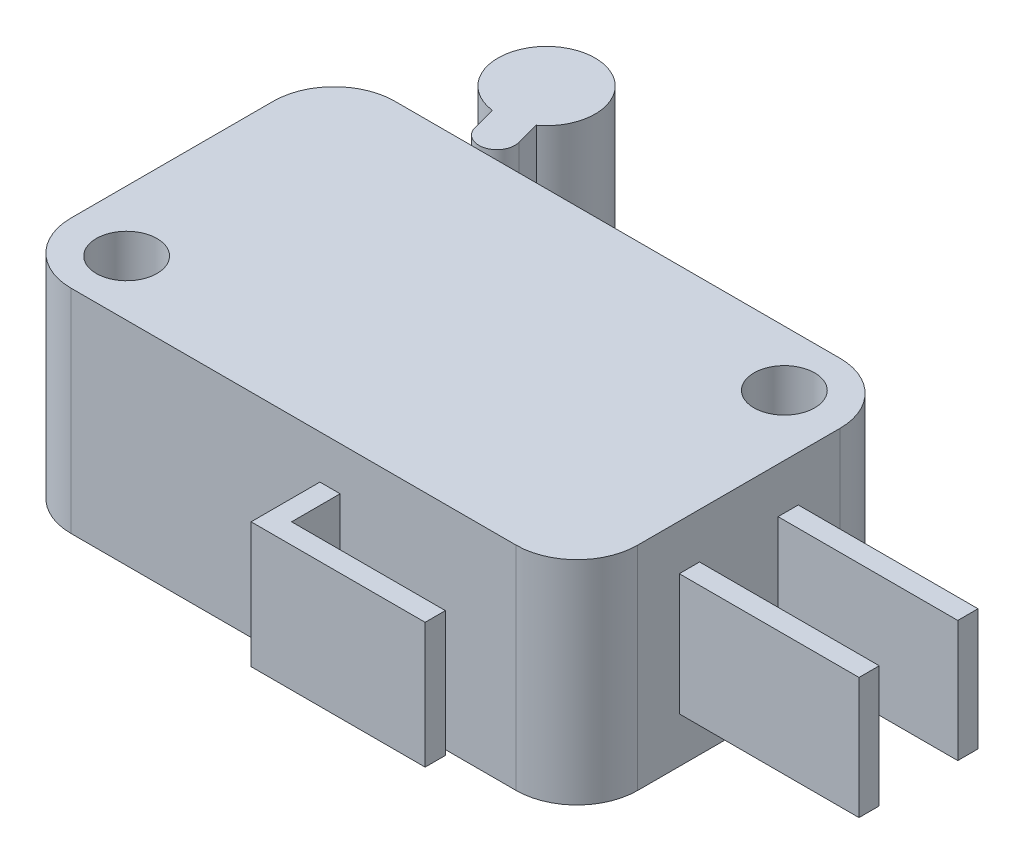
SolidWorks part; units mm, degrees
other "标注1"
sketch "草图9" plane through (22.88, 5.25, -16.5) normal (0.284, 0.954, -0.0961) x (0.0916, -0.1268, -0.9877)
material "304不锈钢"
ref_plane "前视基准面" through (0, 0, 0) normal (0, 0, 1) x (1, 0, 0)
ref_plane "上视基准面" through (0, 0, 0) normal (0, 1, 0) x (1, 0, 0)
ref_plane "右视基准面" through (0, 0, 0) normal (1, 0, 0) x (0, 0, -1)
sketch "草图1" plane through (0, 0, 0) normal (0, 1, 0) x (1, 0, 0)
  line L1 (-14, 8) -> (14, 8)
  line L2 (-14, 8) -> (-14, -8)
  line L3 (-14, -8) -> (14, -8)
  line L4 (14, 8) -> (14, -8)
  line L5 (-14, 8) -> (14, -8) construction
  line L6 (-14, -8) -> (14, 8) construction
  point P0 (0, 0)
  dimension "D1" = 16
  dimension "D2" = 28
extrude "凸台-拉伸1" add sketch "草图1" along normal mid plane 10.5
fillet "圆角1" radius 3 4 edges at (14, 0, 8) (-14, 0, -8) (14, 0, -8) (-14, 0, 8)
sketch "草图2" plane through (0, 5.25, 0) normal (0, 1, 0) x (1, 0, 0)
  line L1 (-11, -5.25) -> (11, -5.25) construction
  line L2 (-11, -5.25) -> (-11, 5.25) construction
  line L3 (-11, 5.25) -> (11, 5.25) construction
  line L4 (11, -5.25) -> (11, 5.25) construction
  line L5 (0, 5.25) -> (0, -5.25) construction
  line L6 (-11, 0) -> (11, 0) construction
  circle A0 centre (11, 5.25) radius 1.5
  circle A1 centre (-11, -5.25) radius 1.5
  point P2 (0, 0)
  dimension "D1" = 3
  dimension "D2" = 3
  dimension "D3" = 10.5
  dimension "D4" = 22
extrude "切除-拉伸1" cut sketch "草图2" against normal up to next
sketch "草图3" plane through (0, 0, 8) normal (0, 0, 1) x (1, 0, 0)
  line L0 (-14, -5.25) -> (-14, 5.25) construction
  line L1 (1.3, 3.1) -> (9.9, 3.1)
  line L2 (1.3, 3.1) -> (1.3, -3.1)
  line L3 (1.3, -3.1) -> (9.9, -3.1)
  line L4 (9.9, 3.1) -> (9.9, -3.1)
  line L5 (1.3, 3.1) -> (9.9, -3.1) construction
  line L6 (1.3, -3.1) -> (9.9, 3.1) construction
  point P0 (5.6, 0)
  dimension "D1" = 6.2
  dimension "D2" = 8.6
  dimension "D3" = 15.3
extrude "凸台-拉伸2" add sketch "草图3" along normal blind 3.4
sketch "草图4" plane through (0, 3.1, 0) normal (0, 1, 0) x (1, 0, 0)
  line L0 (9.9, -11.4) -> (1.3, -11.4) construction
  line L1 (9.9, -8) -> (2.3, -8)
  line L2 (9.9, -8) -> (9.9, -10.4)
  line L3 (9.9, -10.4) -> (2.3, -10.4)
  line L4 (2.3, -8) -> (2.3, -10.4)
  line L5 (1.3, -11.4) -> (1.3, -8) construction
  dimension "D1" = 1
  dimension "D2" = 1
extrude "切除-拉伸2" cut sketch "草图4" against normal up to next
sketch "草图5" plane through (0, 0, 0) normal (0, 1, 0) x (1, 0, 0)
  line L0 (14, -5) -> (14, 5) construction
  line L1 (14, 2.94) -> (22.88, 2.94)
  line L2 (14, 2.94) -> (14, 1.94)
  line L3 (14, 1.94) -> (22.88, 1.94)
  line L4 (22.88, 2.94) -> (22.88, 1.94)
  line L5 (-14, 5) -> (-14, -5) construction
  line L6 (14, -1.94) -> (22.88, -1.94)
  line L7 (14, -1.94) -> (14, -2.94)
  line L8 (14, -2.94) -> (22.88, -2.94)
  line L9 (22.88, -1.94) -> (22.88, -2.94)
  line L10 (14, 1.94) -> (14, -1.94) construction
  point P12 (14, 0)
  dimension "D1" = 1
  dimension "D2" = 1
  dimension "D3" = 5.88
  dimension "D4" = 36.88
extrude "凸台-拉伸3" add sketch "草图5" along normal mid plane 6
sketch "草图6" plane through (0, 0, -8) normal (0, 0, -1) x (-1, 0, 0)
  line L0 (14, 5.25) -> (14, -5.25) construction
  line L1 (11.3, 2.1) -> (8.5, 2.1)
  line L2 (11.3, 2.1) -> (11.3, -2.1)
  line L3 (11.3, -2.1) -> (8.5, -2.1)
  line L4 (8.5, 2.1) -> (8.5, -2.1)
  line L5 (11.3, 2.1) -> (8.5, -2.1) construction
  line L6 (11.3, -2.1) -> (8.5, 2.1) construction
  point P0 (9.9, 0)
  dimension "D1" = 2.8
  dimension "D2" = 5.5
  dimension "D3" = 4.2
extrude "凸台-拉伸4" add sketch "草图6" along normal blind 3
fillet "圆角2" radius 1.2 2 edges at (-11.3, 0, -11) (-8.5, 0, -11)
sketch "草图7" plane through (0, 0, 0) normal (0, 1, 0) x (1, 0, 0)
  line L0 (2.6, 8) -> (2.6, 9.1858)
  line L1 (11, 8) -> (-11, 8) construction
  line L2 (2.6, 9.1858) -> (-9.5237, 10.987)
  line L3 (14, -5) -> (14, 5) construction
  line L4 (-11, -8) -> (11, -8) construction
  arc A0 (-8.5, 9.8) -> (-9.7, 11) centre (-9.7, 9.8) ccw construction
  circle A1 centre (-9.6, 14.1) radius 2.4
  dimension "D2" = 24.5
  dimension "D3" = 4.8
  dimension "D1" = 11.4
extrude "拉伸-薄壁2" add sketch "草图7" along normal mid plane 3 thin contours L0 L2 thin type mid plane wall 1
extrude "凸台-拉伸5" add sketch "草图7<3>" along normal mid plane 7.1 separate body contours A1 region at (-9.6, 0, -14.1)
sketch "草图7<3>" plane through (0, 0, 0) normal (0, 1, 0) x (1, 0, 0) same geometry as "草图7"
sketch "草图8" plane through (0, 0, 0) normal (0, 1, 0) x (1, 0, 0)
  line L0 (-9.6, 14.1) -> (-8.7294, 10.7764) construction
  line L1 (-8.741, 14.325) -> (-7.8704, 11.0014)
  line L2 (-10.459, 13.875) -> (-9.5883, 10.5514)
  arc A0 (-8.741, 14.325) -> (-10.459, 13.875) centre (-9.6, 14.1) ccw
  arc A1 (-9.5883, 10.5514) -> (-7.8704, 11.0014) centre (-8.7294, 10.7764) ccw
  point P3 (-9.1647, 12.4382)
extrude "凸台-拉伸6" add sketch "草图8" along normal mid plane 7.1
